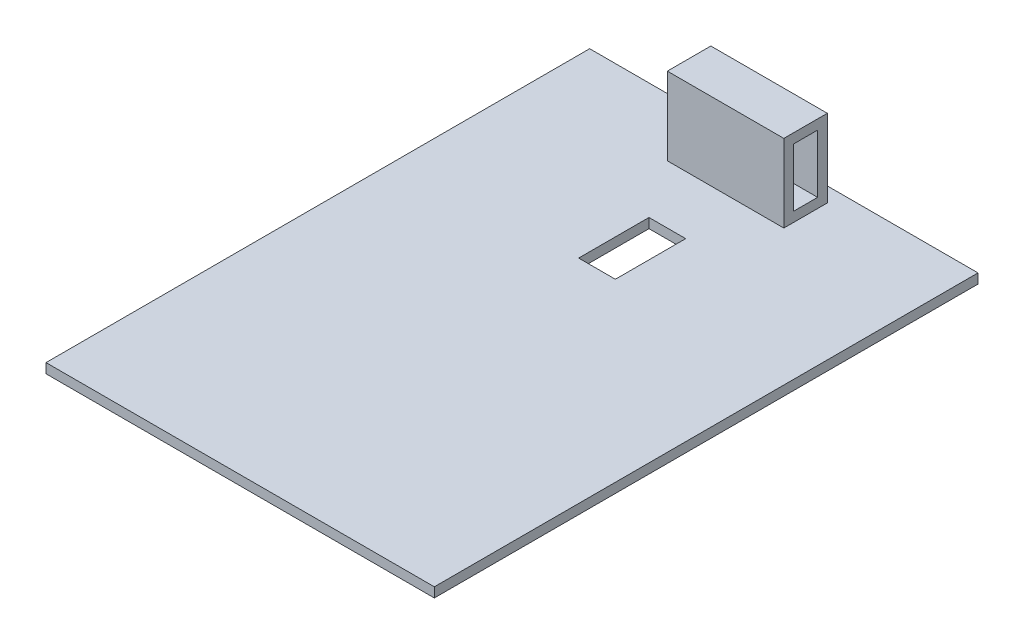
SolidWorks part; units mm, degrees
ref_plane "Front Plane" through (0, 0, 0) normal (0, 0, 1) x (1, 0, 0)
ref_plane "Top Plane" through (0, 0, 0) normal (0, 1, 0) x (1, 0, 0)
ref_plane "Right Plane" through (0, 0, 0) normal (1, 0, 0) x (0, 0, -1)
sketch "Sketch1" plane through (0, 0, 0) normal (0, 1, 0) x (1, 0, 0)
  line L0 (63.5, 177.8) -> (63.5, 0) construction
  line L1 (0, 0) -> (127, 0)
  line L2 (0, 0) -> (0, 177.8)
  line L3 (0, 177.8) -> (127, 177.8)
  line L4 (127, 0) -> (127, 177.8)
  line L5 (57.5, 139.7) -> (69.5, 139.7)
  line L6 (57.5, 139.7) -> (57.5, 116.7)
  line L7 (57.5, 116.7) -> (69.5, 116.7)
  line L8 (69.5, 139.7) -> (69.5, 116.7)
  line L9 (63.5, 139.7) -> (63.5, 116.7) construction
  dimension "D1" = 127
  dimension "D2" = 177.8
  dimension "D3" = 12
  dimension "D4" = 23
  dimension "D5" = 38.1
extrude "Boss-Extrude2" add sketch "Sketch1" along normal blind 3.175
ref_plane "Plane1" through (0, 0, -158.75) normal (0, 0, -1) x (-1, 0, 0)
sketch "Sketch5" plane through (0, 0, -158.75) normal (0, 0, -1) x (-1, 0, 0)
  line L0 (-127, 3.175) -> (0, 3.175) construction
  line L1 (-82.55, 28.575) -> (-44.45, 28.575)
  line L2 (-82.55, 28.575) -> (-82.55, 3.175)
  line L3 (-82.55, 3.175) -> (-44.45, 3.175)
  line L4 (-44.45, 28.575) -> (-44.45, 3.175)
  line L5 (-63.5, 28.575) -> (-63.5, 3.175) construction
  line L6 (-63.5, 3.175) -> (-63.5, 0) construction
  line L7 (-127, 0) -> (0, 0) construction
  dimension "D1" = 25.4
  dimension "D2" = 38.1
extrude "Boss-Extrude3" add sketch "Sketch5" along normal blind 14.224
sketch "Sketch8" plane through (82.55, 0, 0) normal (1, 0, 0) x (0, 0, -1)
  line L0 (172.974, 28.575) -> (172.974, 3.175) construction
  line L1 (161.925, 25.4) -> (169.799, 25.4)
  line L2 (161.925, 25.4) -> (161.925, 6.35)
  line L3 (161.925, 6.35) -> (169.799, 6.35)
  line L4 (169.799, 25.4) -> (169.799, 6.35)
  line L5 (172.974, 28.575) -> (158.75, 28.575) construction
  line L9 (158.75, -22.942) -> (158.75, 22.942) construction
  line L10 (172.974, 3.175) -> (158.75, 3.175) construction
  dimension "D1" = 3.175
  dimension "D2" = 3.175
  dimension "D3" = 3.175
  dimension "D4" = 3.175
extrude "Cut-Extrude1" cut sketch "Sketch8" against normal up to next
